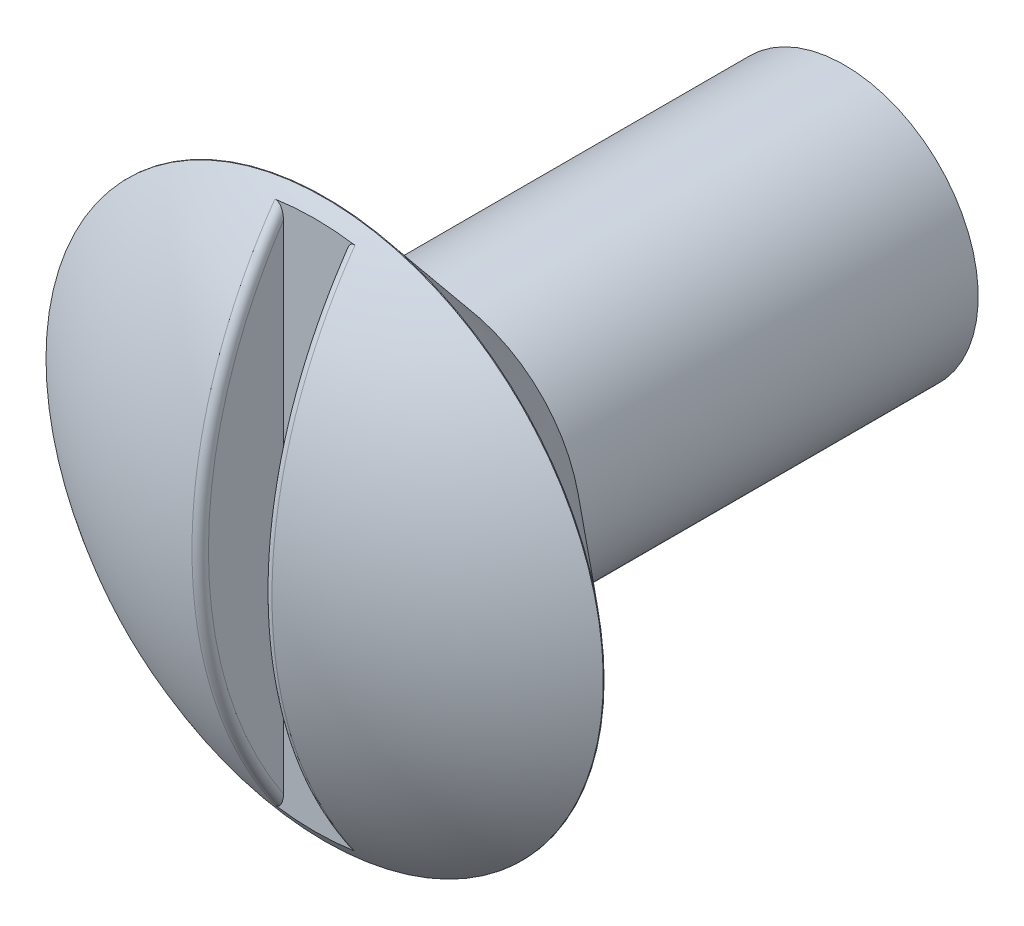
SolidWorks part; units mm, degrees
ref_plane "Front" through (0, 0, 0) normal (0, 0, 1) x (1, 0, 0)
ref_plane "Top" through (0, 0, 0) normal (0, 1, 0) x (1, 0, 0)
ref_plane "Right" through (0, 0, 0) normal (1, 0, 0) x (0, 0, -1)
sketch "Sketch1" plane through (0, 0, 0) normal (0, 0, 1) x (1, 0, 0)
  circle A0 centre (0, 0) radius 3.5433
  dimension "D1" = 7.0866
extrude "Boss-Extrude1" add sketch "Sketch1" along normal blind 0.01
dome "Dome1" faces to dome 1 distance 1.2 reverse direction no elliptical dome no face at (3.5433, 0, 0.01) parameters "D1"=1.2
fillet "Fillet1" [suppressed] radius 0.2
sketch "Sketch2" plane through (0, 0, 0) normal (0, 0, -1) x (-1, 0, 0)
  circle A1 centre (0, 0) radius 3.5433
  circle A2 centre (0, 0) radius 3.5433
  dimension "D1" = 0
extrude "Boss-Extrude2" add sketch "Sketch2" along normal blind 1.5 draft 50
sketch "Sketch3" plane through (0, 0, -1.5) normal (0, 0, -1) x (-1, 0, 0)
  circle A0 centre (0, 0) radius 1.7
  dimension "D1" = 3.4
extrude "Boss-Extrude3" add sketch "Sketch3" along normal blind 5.1
ref_plane "Plane1" through (0, 0, 0.1339) normal (0, 0, 1) x (1, 0, 0)
sketch "Sketch4" plane through (0, 0, 0.1339) normal (0, 0, 1) x (1, 0, 0)
  line L0 (0, 0) -> (0, 3.8) construction
  line L2 (-0.4, 3.8) -> (0.4, 3.8)
  line L3 (-0.4, 3.8) -> (-0.4, -3.8)
  line L4 (-0.4, -3.8) -> (0.4, -3.8)
  line L5 (0.4, 3.8) -> (0.4, -3.8)
  dimension "D1" = 0.8
  dimension "D2" = 7.6
  dimension "D3" = 3.8
extrude "Cut-Extrude1" cut sketch "Sketch4" along normal blind 3
fillet "Fillet3" radius 0.1 2 edges at (-0.4, 0, 1.1963) (0.4, 0, 1.1963)
